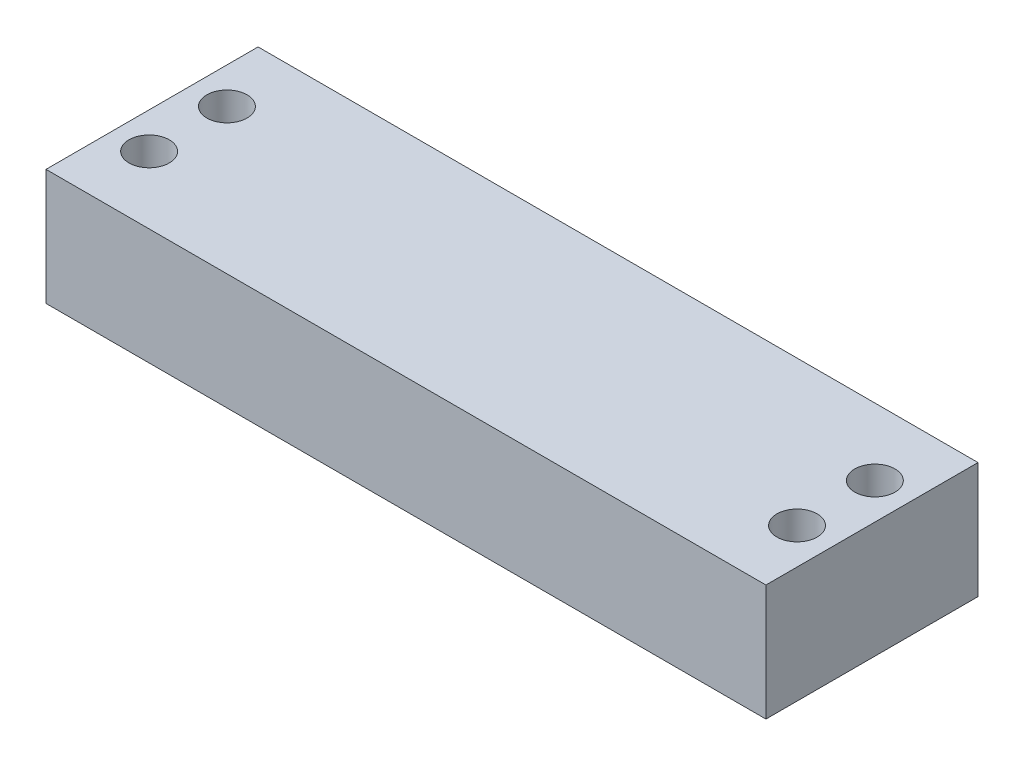
SolidWorks part; units mm, degrees
ref_plane "Front Plane" through (0, 0, 0) normal (0, 0, 1) x (1, 0, 0)
ref_plane "Top Plane" through (0, 0, 0) normal (0, 1, 0) x (1, 0, 0)
ref_plane "Right Plane" through (0, 0, 0) normal (1, 0, 0) x (0, 0, -1)
sketch "Sketch1" plane through (0, 0, 0) normal (0, 1, 0) x (1, 0, 0)
  line L0 (0, 10.9) -> (74, 10.9) construction
  line L1 (0, 0) -> (74, 0)
  line L2 (0, 0) -> (0, 21.8)
  line L3 (0, 21.8) -> (74, 21.8)
  line L4 (74, 0) -> (74, 21.8)
  line L5 (37, 21.8) -> (37, 0) construction
  line L6 (0, 6.9) -> (74, 6.9) construction
  line L7 (3.7, 21.8) -> (3.7, 0) construction
  circle A0 centre (3.7, 6.9) radius 2.0701
  circle A1 centre (3.7, 14.9) radius 2.0701
  circle A2 centre (70.3, 6.9) radius 2.0701
  circle A3 centre (70.3, 14.9) radius 2.0701
  point P13 (3.7, 6.9)
  point P19 (0, 0)
  dimension "D3" = 4.1402
  dimension "D1" = 74
  dimension "D2" = 21.8
  dimension "D4" = 33.3
  dimension "D5" = 4
extrude "Boss-Extrude1" add sketch "Sketch1" along normal blind 11.938
ref_plane "Plane1" through (0, 0, -10.9) normal (0, 0, 1) x (1, 0, 0)
